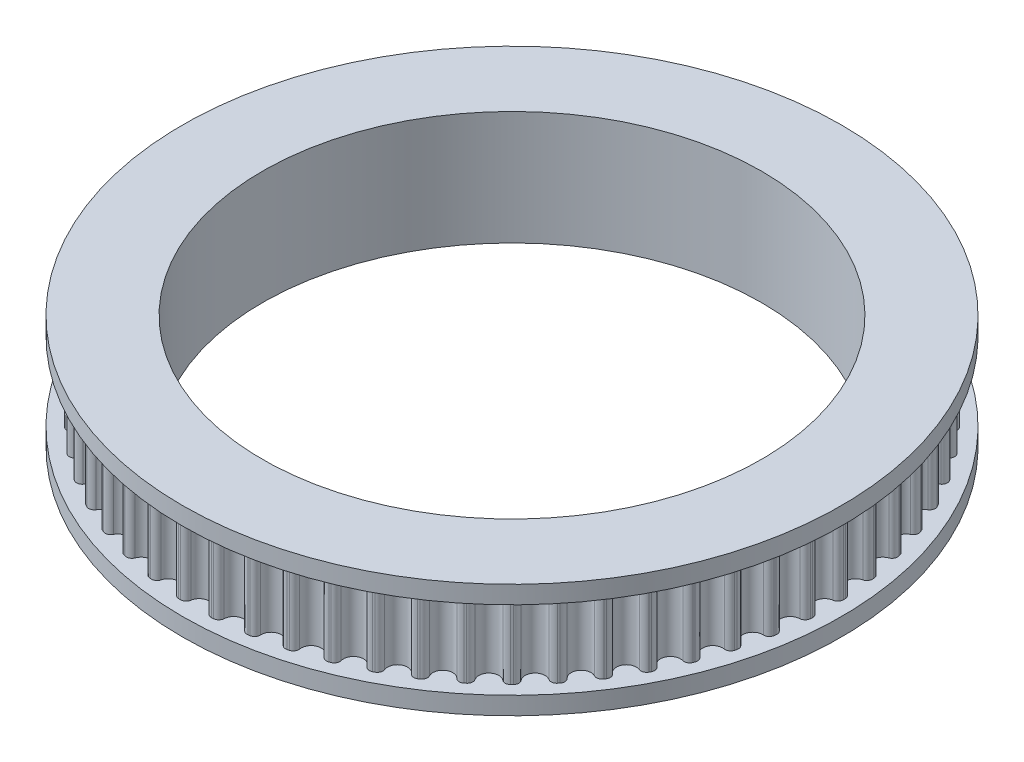
SolidWorks part; units mm, degrees
ref_plane "Front Plane" through (0, 0, 0) normal (0, 0, 1) x (1, 0, 0)
ref_plane "Top Plane" through (0, 0, 0) normal (0, 1, 0) x (1, 0, 0)
ref_plane "Right Plane" through (0, 0, 0) normal (1, 0, 0) x (0, 0, -1)
sketch "Sketch1" plane through (0, 0, 0) normal (0, 1, 0) x (1, 0, 0)
  line L0 (0, 0) -> (0, 28.2667) construction
  line L1 (0, 0) -> (2.9202, 27.7837) construction
  circle A0 centre (0, 0) radius 28.2667 construction
  circle A1 centre (0, 0) radius 27.0467 construction
  circle A2 centre (0, 27.9367) radius 0.89 construction
  circle A5 centre (2.9202, 27.7837) radius 0.89 construction
  arc A6 (0, 27.0467) -> (0.8804, 27.8061) centre (0, 27.9367) ccw
  arc A7 (0.8804, 27.8061) -> (1.3997, 28.2321) centre (1.3749, 27.7327) cw
  arc A8 (1.559, 28.2237) -> (2.031, 27.7458) centre (1.5314, 27.7245) cw
  arc A9 (2.8272, 26.8986) -> (2.031, 27.7458) centre (2.9202, 27.7837) cw
  arc A10 (1.3997, 28.2321) -> (1.559, 28.2237) centre (0, 0) cw
  arc A11 (0, 27.0467) -> (2.8272, 26.8986) centre (0, 0) ccw
  dimension "D1" = 56.5335
  dimension "D3" = 1.78
  dimension "D4" = 0.5
  dimension "D2" = 1.22
  dimension "D5" = 6
extrude "Boss-Extrude1" add sketch "Sketch1" along normal mid plane 7 contours A6 A11 A9 A8 A7 region at (0.001, 0, -0.0192)
ref_axis "Axis1" through (0, 3.3, 0) along (0, -1, 0)
pattern_circular "CirPattern1" count 60 over 360 about axis through (0, 3.3, 0) along (0, -1, 0) of "Boss-Extrude1"
sketch "Sketch2" plane through (0, 0, 0) normal (1, 0, 0) x (0, 0, -1)
  line L10 (0, 3.5) -> (29.4415, 3.5) construction
  line L11 (0, 3.5) -> (0, 5.0875) construction
  line L12 (0, 5.0875) -> (29.4415, 5.0875) construction
  line L15 (29.4415, 3.5) -> (29.4415, 5.0875) construction
  line L20 (0, 3.3) -> (0, -3.3) construction
  line L22 (29.4415, 5.0875) -> (0, 5.0875)
  line L23 (29.4415, 5.0875) -> (29.4415, 3.5)
  line L24 (29.4415, 3.5) -> (0, 3.5)
  line L25 (0, 5.0875) -> (0, 3.5)
  dimension "D1" = 1.5875
  dimension "D2" = 29.4415
  dimension "D3" = 3.5
revolve "Revolve3" add sketch "Sketch2" angle 360 about axis through (0, 3.3, 0) along (0, -1, 0) region at (0, 4.2937, -14.7207)
mirror "Mirror1" about plane through (0, 0, 0) normal (0, 1, 0) of "Revolve3"
sketch "Sketch3" plane through (0, 0, 0) normal (0, -1, 0) x (-1, 0, 0)
  circle A0 centre (0, 0) radius 22.2977
  dimension "D1" = 44.5955
extrude "Cut-Extrude1" cut sketch "Sketch3" against normal through all both and the other way through all
ref_axis "Axis2" through (0, 5.0875, 0) along (0, -1, 0)
ref_plane "Plane1" through (0, 0, 0) normal (-0.9284, 0, -0.3715) x (0, -1, 0)
equation "\"TEETH_NUM\"= 60"
equation "\"TOOTH_PITCH\"= 3mm"
equation "\"PITCH_LINE_OFFSET\"= .015in"
equation "\"DIAMETER_PER_GROOVE\"= \"OUTSIDE_DIAMETER\" / \"TEETH_NUM\" * 1in"
equation "\"PITCH_DIAMETER\"= ( ( \"TEETH_NUM\" * 3 - 1.31 ) / 3.1415 + .415 ) * 1mm"
equation "\"OUTSIDE_DIAMETER\"= \"PITCH_DIAMETER\" - \"PITCH_LINE_OFFSET\" * 2"
equation "\"D1@Sketch1\"=\"OUTSIDE_DIAMETER\""
equation "\"TOOTH_HEIGHT\"= 1.22mm"
equation "\"D2@Sketch1\"=\"TOOTH_HEIGHT\""
equation "\"TOOTH_DIAMETER\"= 1.78mm"
equation "\"INTERNAL_RADIUS\"= .5mm"
equation "\"D3@Sketch1\"=\"TOOTH_DIAMETER\""
equation "\"D5@Sketch1\"=360 / \"TEETH_NUM\""
equation "\"D4@Sketch1\"=\"INTERNAL_RADIUS\""
equation "\"D1@CirPattern1\"=\"TEETH_NUM\""
equation "\"BELT_GAP\"= 7mm"
equation "\"D2@Sketch2\"=\"PITCH_DIAMETER\"/2+1/32"
equation "\"D3@Sketch2\"=\"BELT_GAP\"/2"
equation "\"D1@Sketch3\"=\"PITCH_DIAMETER\"-.5"
equation "\"D1@Boss-Extrude1\"=\"BELT_GAP\""
